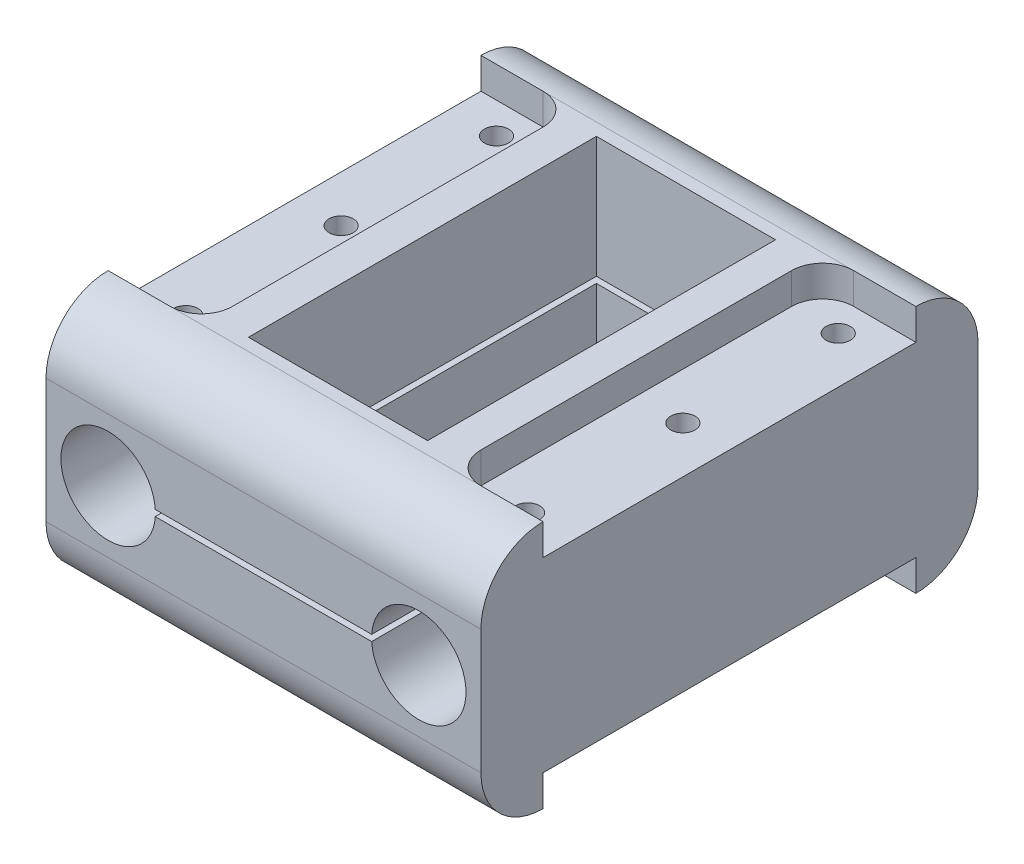
SolidWorks part; units mm, degrees
ref_plane "Front Plane" through (0, 0, 0) normal (0, 0, 1) x (1, 0, 0)
ref_plane "Top Plane" through (0, 0, 0) normal (0, 1, 0) x (1, 0, 0)
ref_plane "Right Plane" through (0, 0, 0) normal (1, 0, 0) x (0, 0, -1)
sketch "Sketch1" plane through (0, 0, 0) normal (0, 0, 1) x (1, 0, 0)
  line L0 (0, 0) -> (50, 0) construction
  line L2 (-10, 20) -> (60, 20)
  line L3 (-10, 20) -> (-10, -20)
  line L4 (-10, -20) -> (60, -20)
  line L5 (60, 20) -> (60, -20)
  line L6 (-10, 20) -> (60, -20) construction
  line L7 (-10, -20) -> (60, 20) construction
  circle A0 centre (0, 0) radius 7.6
  circle A1 centre (50, 0) radius 7.6
  point P5 (25, 0)
  dimension "D1" = 15.2
  dimension "D2" = 50
  dimension "D3" = 70
  dimension "D4" = 40
extrude "Boss-Extrude1" add sketch "Sketch1" along normal blind 80
fillet "Fillet1" radius 10 4 edges at (25, 20, 80) (25, -20, 80) (25, -20, 0) (25, 20, 0)
sketch "Sketch12" plane through (0, 0, 80) normal (0, 0, 1) x (1, 0, 0)
  line L0 (7.6, 0) -> (42.4, 0)
  line L1 (7.6, 0) -> (3.1193, 0)
  line L2 (42.4, 0) -> (46.982, 0)
  circle A0 centre (0, 0) radius 7.6 construction
  circle A1 centre (50, 0) radius 7.6 construction
extrude "Cut-Extrude-Thin1" cut sketch "Sketch12" against normal blind 95 and the other way through all thin thin type mid plane wall 1
sketch "Sketch24" plane through (0, 0.5, 0) normal (0, -1, 0) x (1, 0, 0)
  line L1 (10.5835, 68) -> (10.5835, 12)
  line L3 (39.4165, 12) -> (39.4165, 68)
  line L4 (7.5835, 80) -> (7.5835, 0)
  line L5 (7.5835, 0) -> (42.4165, 0)
  line L6 (42.4165, 0) -> (42.4165, 80)
  line L7 (42.4165, 80) -> (7.5835, 80)
  line L8 (7.5835, 80) -> (7.5835, 0)
  line L9 (7.5835, 0) -> (42.4165, 0)
  line L10 (42.4165, 0) -> (42.4165, 80)
  line L11 (42.4165, 80) -> (7.5835, 80)
  line L12 (10.5835, 68) -> (39.4165, 68)
  line L13 (10.5835, 12) -> (39.4165, 12)
  line L14 (10.5835, 77) -> (10.5835, 3) construction
  line L15 (39.4165, 3) -> (39.4165, 77) construction
  line L16 (39.4165, 77) -> (10.5835, 77) construction
  line L17 (10.5835, 3) -> (39.4165, 3) construction
  dimension "D3" = 12
  dimension "D4" = 12
  dimension "D1" = 0
  dimension "D2" = 3
extrude "Cut-Extrude15" cut sketch "Sketch24" against normal blind 40 and the other way blind 39 contours L3 L1 region at (25, 0.5, 40)
sketch "Sketch27" plane through (0, 20, 0) normal (0, 1, 0) x (1, 0, 0)
  line L0 (-10, -70) -> (60, -70) construction
  line L1 (-10, -10) -> (0, -10)
  line L2 (-10, -10) -> (-10, -70)
  line L3 (-10, -70) -> (0, -70)
  line L4 (5, -15) -> (5, -65)
  arc A0 (0, -70) -> (5, -65) centre (0, -65) ccw
  arc A1 (0, -10) -> (5, -15) centre (0, -15) cw
  point P9 (5, -70)
  point P12 (5, -10)
  dimension "D2" = 5
  dimension "D1" = 15
extrude "Cut-Extrude17" cut sketch "Sketch27" against normal blind 5
sketch "Sketch28" plane through (0, 15, 0) normal (0, 1, 0) x (1, 0, 0)
  line L0 (5, -15) -> (-2.5, -15) construction
  line L1 (5, -40) -> (-2.5, -40) construction
  line L2 (5, -65) -> (5, -15) construction
  line L3 (5, -65) -> (-2.5, -65) construction
  circle A0 centre (-2.5, -15) radius 1.95
  circle A1 centre (-2.5, -40) radius 1.95
  circle A2 centre (-2.5, -65) radius 1.95
  dimension "D2" = 3.9
  dimension "D1" = 7.5
extrude "Cut-Extrude18" cut sketch "Sketch28" against normal blind 20
ref_plane "Plane2" through (25, 0, 0) normal (-1, 0, 0) x (0, 0, 1)
mirror "Mirror1" about plane through (25, 0, 0) normal (-1, 0, 0) of "Cut-Extrude17", "Cut-Extrude18"
mirror "Mirror2" about plane through (0, 0, 0) normal (0, 1, 0) of "Mirror1"
